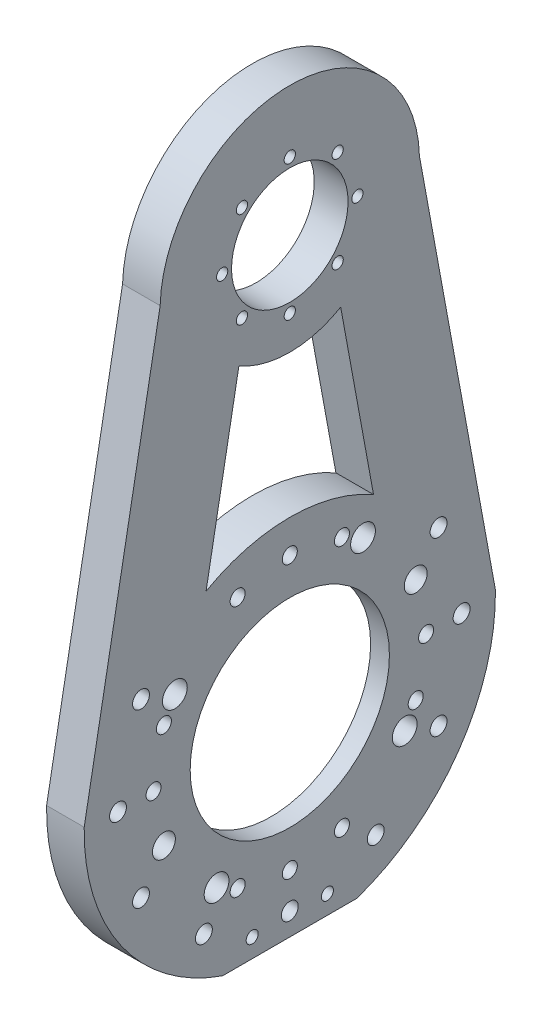
SolidWorks part; units mm, degrees
note: '?' marks a value the reader was unsure of. The reader was unsure of these and kept them because the rebuilt part matched: shared geometry of "Sketch2<5>".
ref_plane "Front Plane" through (0, 0, 0) normal (0, 0, 1) x (1, 0, 0)
ref_plane "Top Plane" through (0, 0, 0) normal (0, 1, 0) x (1, 0, 0)
ref_plane "Right Plane" through (0, 0, 0) normal (1, 0, 0) x (0, 0, -1)
sketch "Sketch2" plane through (0, 0, 0) normal (1, 0, 0) x (0, 0, -1)
  line L7 (-4.0065, 80) -> (3.9935, 80) construction
  line L8 (-44.7, 110) -> (49.7, 110) construction
  line L13 (-67.7, 0) -> (-67.7, 110)
  line L14 (67.7, 110) -> (67.7, 10)
  line L15 (67.7, -68) -> (67.7, 10)
  line L16 (-67.7, -68) -> (67.7, -68)
  line L17 (-67.7, 0) -> (-67.7, -68)
  arc A0 (-15.2865, -32.0764) -> (-12.4581, -34.9048) centre (-13.8723, -33.4906) ccw
  arc A1 (-12.4581, -34.9048) -> (-15.2865, -32.0764) centre (-13.8723, -33.4906) ccw
  arc A74 (3.7195, -20.5317) -> (1.6907, -23.1344) centre (2.7051, -21.8331) ccw
  arc A75 (1.6907, -23.1344) -> (3.7195, -20.5317) centre (2.7051, -21.8331) ccw
  arc A76 (14.2736, -16.2541) -> (12.2448, -18.8568) centre (13.2592, -17.5554) ccw
  arc A77 (12.2448, -18.8568) -> (14.2736, -16.2541) centre (13.2592, -17.5554) ccw
  arc A78 (21.275, -7.2725) -> (19.2461, -9.8752) centre (20.2605, -8.5738) ccw
  arc A79 (19.2461, -9.8752) -> (21.275, -7.2725) centre (20.2605, -8.5738) ccw
  arc A80 (22.8475, 4.0065) -> (20.8186, 1.4038) centre (21.8331, 2.7051) ccw
  arc A81 (20.8186, 1.4038) -> (22.8475, 4.0065) centre (21.8331, 2.7051) ccw
  arc A82 (18.5698, 14.5606) -> (16.541, 11.9579) centre (17.5554, 13.2592) ccw
  arc A83 (16.541, 11.9579) -> (18.5698, 14.5606) centre (17.5554, 13.2592) ccw
  arc A84 (9.5882, 21.5619) -> (7.5594, 18.9592) centre (8.5738, 20.2605) ccw
  arc A85 (7.5594, 18.9592) -> (9.5882, 21.5619) centre (8.5738, 20.2605) ccw
  arc A86 (-1.6907, 23.1344) -> (-3.7195, 20.5317) centre (-2.7051, 21.8331) ccw
  arc A87 (-3.7195, 20.5317) -> (-1.6907, 23.1344) centre (-2.7051, 21.8331) ccw
  arc A88 (-12.2448, 18.8568) -> (-14.2736, 16.2541) centre (-13.2592, 17.5554) ccw
  arc A89 (-14.2736, 16.2541) -> (-12.2448, 18.8568) centre (-13.2592, 17.5554) ccw
  arc A90 (-19.2461, 9.8752) -> (-21.275, 7.2725) centre (-20.2605, 8.5738) ccw
  arc A91 (-21.275, 7.2725) -> (-19.2461, 9.8752) centre (-20.2605, 8.5738) ccw
  arc A92 (-20.8186, -1.4038) -> (-22.8475, -4.0065) centre (-21.8331, -2.7051) ccw
  arc A93 (-22.8475, -4.0065) -> (-20.8186, -1.4038) centre (-21.8331, -2.7051) ccw
  arc A94 (-16.541, -11.9579) -> (-18.5698, -14.5606) centre (-17.5554, -13.2592) ccw
  arc A95 (-18.5698, -14.5606) -> (-16.541, -11.9579) centre (-17.5554, -13.2592) ccw
  arc A96 (-7.5594, -18.9592) -> (-9.5882, -21.5619) centre (-8.5738, -20.2605) ccw
  arc A97 (-9.5882, -21.5619) -> (-7.5594, -18.9592) centre (-8.5738, -20.2605) ccw
  arc A98 (28.2395, -17.1437) -> (32.9064, -21.8106) centre (30.5729, -19.4771) ccw
  arc A99 (32.9064, -21.8106) -> (28.2395, -17.1437) centre (30.5729, -19.4771) ccw
  arc A102 (17.1437, 32.9064) -> (21.8106, 28.2395) centre (19.4771, 30.5729) ccw
  arc A103 (21.8106, 28.2395) -> (17.1437, 32.9064) centre (19.4771, 30.5729) ccw
  arc A104 (-32.9064, 21.8106) -> (-28.2395, 17.1437) centre (-30.5729, 19.4771) ccw
  arc A105 (-28.2395, 17.1437) -> (-32.9064, 21.8106) centre (-30.5729, 19.4771) ccw
  arc A108 (-21.8106, -28.2395) -> (-17.1437, -32.9064) centre (-19.4771, -30.5729) ccw
  arc A109 (-17.1437, -32.9064) -> (-21.8106, -28.2395) centre (-19.4771, -30.5729) ccw
  arc A110 (-16.2921, -20.9002) -> (16.2921, 20.9002) centre (0, 0) ccw
  arc A111 (16.2921, 20.9002) -> (-16.2921, -20.9002) centre (0, 0) ccw
  circle A112 centre (0, 0) radius 40.5
  arc A113 (31.334, 16.029) -> (35.6473, 11.7156) centre (33.4906, 13.8723) ccw
  arc A114 (1.4142, -37.6642) -> (-1.4142, -34.8358) centre (0, -36.25) ccw
  arc A115 (-1.4142, -34.8358) -> (1.4142, -37.6642) centre (0, -36.25) ccw
  arc A116 (15.2865, -34.9048) -> (12.4581, -32.0764) centre (13.8723, -33.4906) ccw
  arc A117 (12.4581, -32.0764) -> (15.2865, -34.9048) centre (13.8723, -33.4906) ccw
  arc A118 (32.0764, -12.4581) -> (34.9048, -15.2865) centre (33.4906, -13.8723) ccw
  arc A119 (34.9048, -15.2865) -> (32.0764, -12.4581) centre (33.4906, -13.8723) ccw
  arc A120 (37.6642, -1.4142) -> (34.8358, 1.4142) centre (36.25, 0) ccw
  arc A121 (34.8358, 1.4142) -> (37.6642, -1.4142) centre (36.25, 0) ccw
  arc A122 (15.2865, 32.0764) -> (12.4581, 34.9048) centre (13.8723, 33.4906) ccw
  arc A123 (12.4581, 34.9048) -> (15.2865, 32.0764) centre (13.8723, 33.4906) ccw
  arc A124 (1.4142, 34.8358) -> (-1.4142, 37.6642) centre (0, 36.25) ccw
  arc A125 (-1.4142, 37.6642) -> (1.4142, 34.8358) centre (0, 36.25) ccw
  arc A126 (-12.4581, 32.0764) -> (-15.2865, 34.9048) centre (-13.8723, 33.4906) ccw
  arc A127 (-15.2865, 34.9048) -> (-12.4581, 32.0764) centre (-13.8723, 33.4906) ccw
  arc A128 (-34.9048, 15.2865) -> (-32.0764, 12.4581) centre (-33.4906, 13.8723) ccw
  arc A129 (-32.0764, 12.4581) -> (-34.9048, 15.2865) centre (-33.4906, 13.8723) ccw
  arc A130 (-34.8358, -1.4142) -> (-37.6642, 1.4142) centre (-36.25, 0) ccw
  arc A131 (-37.6642, 1.4142) -> (-34.8358, -1.4142) centre (-36.25, 0) ccw
  arc A134 (35.6473, 11.7156) -> (31.334, 16.029) centre (33.4906, 13.8723) ccw
  arc A135 (-31.334, -16.029) -> (-35.6473, -11.7156) centre (-33.4906, -13.8723) ccw
  arc A136 (-35.6473, -11.7156) -> (-31.334, -16.029) centre (-33.4906, -13.8723) ccw
  circle A139 centre (0, 110) radius 15.5
  arc A141 (67.7, 110) -> (-67.7, 110) centre (0, 110) ccw
  dimension "D4" = 31
  dimension "D3" = 30
extrude "Boss-Extrude1" add sketch "Sketch2" along normal blind 5
extrude "Boss-Extrude2" add sketch "Sketch2<5>" against normal blind 5
sketch "Sketch2<5>" plane through (0, 0, 0) normal (1, 0, 0) x (0, 0, -1) same geometry as "Sketch2"
sketch "Sketch7" plane through (5, 0, 0) normal (1, 0, 0) x (0, 0, -1)
  arc A0 (-32.0764, 15.2865) -> (-34.9048, 12.4581) centre (-33.4906, 13.8723) ccw
  arc A1 (-34.9048, 12.4581) -> (-32.0764, 15.2865) centre (-33.4906, 13.8723) ccw
  arc A2 (-20.5317, -3.7195) -> (-23.1344, -1.6907) centre (-21.8331, -2.7051) ccw
  arc A3 (-23.1344, -1.6907) -> (-20.5317, -3.7195) centre (-21.8331, -2.7051) ccw
  arc A4 (-16.2541, -14.2736) -> (-18.8568, -12.2448) centre (-17.5554, -13.2592) ccw
  arc A5 (-18.8568, -12.2448) -> (-16.2541, -14.2736) centre (-17.5554, -13.2592) ccw
  arc A6 (-7.2725, -21.275) -> (-9.8752, -19.2461) centre (-8.5738, -20.2605) ccw
  arc A7 (-9.8752, -19.2461) -> (-7.2725, -21.275) centre (-8.5738, -20.2605) ccw
  arc A8 (4.0065, -22.8475) -> (1.4038, -20.8186) centre (2.7051, -21.8331) ccw
  arc A9 (1.4038, -20.8186) -> (4.0065, -22.8475) centre (2.7051, -21.8331) ccw
  arc A10 (14.5606, -18.5698) -> (11.9579, -16.541) centre (13.2592, -17.5554) ccw
  arc A11 (11.9579, -16.541) -> (14.5606, -18.5698) centre (13.2592, -17.5554) ccw
  arc A12 (21.5619, -9.5882) -> (18.9592, -7.5594) centre (20.2605, -8.5738) ccw
  arc A13 (18.9592, -7.5594) -> (21.5619, -9.5882) centre (20.2605, -8.5738) ccw
  arc A14 (23.1344, 1.6907) -> (20.5317, 3.7195) centre (21.8331, 2.7051) ccw
  arc A15 (20.5317, 3.7195) -> (23.1344, 1.6907) centre (21.8331, 2.7051) ccw
  arc A16 (18.8568, 12.2448) -> (16.2541, 14.2736) centre (17.5554, 13.2592) ccw
  arc A17 (16.2541, 14.2736) -> (18.8568, 12.2448) centre (17.5554, 13.2592) ccw
  arc A18 (9.8752, 19.2461) -> (7.2725, 21.275) centre (8.5738, 20.2605) ccw
  arc A19 (7.2725, 21.275) -> (9.8752, 19.2461) centre (8.5738, 20.2605) ccw
  arc A20 (-1.4038, 20.8186) -> (-4.0065, 22.8475) centre (-2.7051, 21.8331) ccw
  arc A21 (-4.0065, 22.8475) -> (-1.4038, 20.8186) centre (-2.7051, 21.8331) ccw
  arc A22 (-11.9579, 16.541) -> (-14.5606, 18.5698) centre (-13.2592, 17.5554) ccw
  arc A23 (-14.5606, 18.5698) -> (-11.9579, 16.541) centre (-13.2592, 17.5554) ccw
  arc A24 (-18.9592, 7.5594) -> (-21.5619, 9.5882) centre (-20.2605, 8.5738) ccw
  arc A25 (-21.5619, 9.5882) -> (-18.9592, 7.5594) centre (-20.2605, 8.5738) ccw
  arc A26 (-17.1437, -28.2395) -> (-21.8106, -32.9064) centre (-19.4771, -30.5729) ccw
  arc A27 (-21.8106, -32.9064) -> (-17.1437, -28.2395) centre (-19.4771, -30.5729) ccw
  arc A28 (32.9064, -17.1437) -> (28.2395, -21.8106) centre (30.5729, -19.4771) ccw
  arc A29 (28.2395, -21.8106) -> (32.9064, -17.1437) centre (30.5729, -19.4771) ccw
  arc A30 (21.8106, 32.9064) -> (17.1437, 28.2395) centre (19.4771, 30.5729) ccw
  arc A31 (17.1437, 28.2395) -> (21.8106, 32.9064) centre (19.4771, 30.5729) ccw
  arc A32 (-28.2395, 21.8106) -> (-32.9064, 17.1437) centre (-30.5729, 19.4771) ccw
  arc A33 (-32.9064, 17.1437) -> (-28.2395, 21.8106) centre (-30.5729, 19.4771) ccw
  arc A34 (-20.9002, 16.2921) -> (20.9002, -16.2921) centre (0, 0) ccw
  arc A35 (20.9002, -16.2921) -> (-20.9002, 16.2921) centre (0, 0) ccw
  circle A36 centre (0, 0) radius 40.5
  arc A37 (16.029, -31.334) -> (11.7156, -35.6473) centre (13.8723, -33.4906) ccw
  arc A38 (-37.6642, -1.4142) -> (-34.8358, 1.4142) centre (-36.25, 0) ccw
  arc A39 (-34.8358, 1.4142) -> (-37.6642, -1.4142) centre (-36.25, 0) ccw
  arc A40 (-34.9048, -15.2865) -> (-32.0764, -12.4581) centre (-33.4906, -13.8723) ccw
  arc A41 (-32.0764, -12.4581) -> (-34.9048, -15.2865) centre (-33.4906, -13.8723) ccw
  arc A42 (-12.4581, -32.0764) -> (-15.2865, -34.9048) centre (-13.8723, -33.4906) ccw
  arc A43 (-15.2865, -34.9048) -> (-12.4581, -32.0764) centre (-13.8723, -33.4906) ccw
  arc A44 (-1.4142, -37.6642) -> (1.4142, -34.8358) centre (0, -36.25) ccw
  arc A45 (1.4142, -34.8358) -> (-1.4142, -37.6642) centre (0, -36.25) ccw
  arc A46 (32.0764, -15.2865) -> (34.9048, -12.4581) centre (33.4906, -13.8723) ccw
  arc A47 (34.9048, -12.4581) -> (32.0764, -15.2865) centre (33.4906, -13.8723) ccw
  arc A48 (34.8358, -1.4142) -> (37.6642, 1.4142) centre (36.25, 0) ccw
  arc A49 (37.6642, 1.4142) -> (34.8358, -1.4142) centre (36.25, 0) ccw
  arc A50 (32.0764, 12.4581) -> (34.9048, 15.2865) centre (33.4906, 13.8723) ccw
  arc A51 (34.9048, 15.2865) -> (32.0764, 12.4581) centre (33.4906, 13.8723) ccw
  arc A52 (15.2865, 34.9048) -> (12.4581, 32.0764) centre (13.8723, 33.4906) ccw
  arc A53 (12.4581, 32.0764) -> (15.2865, 34.9048) centre (13.8723, 33.4906) ccw
  arc A54 (-1.4142, 34.8358) -> (1.4142, 37.6642) centre (0, 36.25) ccw
  arc A55 (1.4142, 37.6642) -> (-1.4142, 34.8358) centre (0, 36.25) ccw
  arc A56 (35.1432, 35.1432) -> (-35.1432, -35.1432) centre (0, 0) ccw
  arc A57 (-35.1432, -35.1432) -> (35.1432, 35.1432) centre (0, 0) ccw
  arc A58 (11.7156, -35.6473) -> (16.029, -31.334) centre (13.8723, -33.4906) ccw
  arc A59 (-16.029, 31.334) -> (-11.7156, 35.6473) centre (-13.8723, 33.4906) ccw
  arc A60 (-11.7156, 35.6473) -> (-16.029, 31.334) centre (-13.8723, 33.4906) ccw
sketch "Sketch8" plane through (5, 0, 0) normal (1, 0, 0) x (0, 0, -1)
  line L0 (-0.0065, 60) -> (49.7, 60) construction
  line L1 (35.5, 110) -> (35.5, 60) construction
  line L2 (0, 110) -> (-0.0065, 60) construction
  line L3 (67.7, -68) -> (67.7, 110)
  line L9 (35.5, 110) -> (35.5, 60)
  line L10 (35.5, 60) -> (49.7, 60)
  line L11 (-35.5129, 60.0092) -> (-49.7129, 60.0128)
  line L12 (-35.5, 110.0092) -> (-35.5129, 60.0092)
  line L19 (67.7, -68) -> (67.7, 110)
  line L22 (-67.7, 110) -> (-67.7, -68)
  line L24 (-67.7, 110) -> (-67.7, -68)
  line L25 (-67.7, -68) -> (67.7, -68)
  line L26 (-67.7, -68) -> (67.7, -68)
  arc A1 (67.7, 110) -> (-67.7, 110) centre (0, 110) ccw
  circle A3 centre (0, 110) radius 15.5 construction
  circle A5 centre (0, 110) radius 15.5
  arc A6 (35.5, 110) -> (-35.5, 110.0092) centre (0, 110) ccw
  circle A7 centre (0, 110) radius 35.5 construction
  arc A15 (67.7, 110) -> (-67.7, 110) centre (0, 110) ccw
  dimension "D1" = 0
  dimension "D2" = 20
fillet "Fillet3" radius 1 1 edges at (-5, 0, -40.5)
sketch "Sketch9" plane through (-5, 0, 0) normal (-1, 0, 0) x (0, 0, 1)
  line L0 (0, 103.5) -> (0, 85.5) construction
  line L1 (-11.8762, 85.5) -> (11.8762, 85.5)
  line L2 (-11.8762, 85.5) -> (-11.8762, 38.1338)
  line L3 (-11.8762, 38.1338) -> (11.8762, 38.1338)
  line L4 (11.8762, 85.5) -> (11.8762, 38.1338)
  line L5 (-11.8762, 85.5) -> (11.8762, 71.7865)
  line L6 (11.8762, 71.7865) -> (-11.8762, 71.7865)
  line L7 (-11.8762, 71.7865) -> (11.8762, 58.073)
  line L8 (11.8762, 58.073) -> (-11.8762, 58.073)
  line L9 (-11.8762, 58.073) -> (11.8762, 44.3596)
  line L10 (11.8762, 44.3596) -> (-11.8762, 44.3596)
  line L11 (-11.8762, 44.3596) -> (-0.0004, 37.503)
  line L12 (-11.8762, 83.1906) -> (4.4121, 73.7865)
  line L13 (4.4121, 73.7865) -> (-11.8762, 73.7865)
  line L14 (-11.8762, 69.4771) -> (4.4121, 60.073)
  line L15 (4.4121, 60.073) -> (-11.8762, 60.073)
  line L16 (-11.8762, 55.7636) -> (4.4121, 46.3596)
  line L17 (4.4121, 46.3596) -> (-11.8762, 46.3596)
  line L18 (-11.8762, 42.0502) -> (-5.0928, 38.1338)
  line L19 (-7.8762, 85.5) -> (11.8762, 74.0959)
  line L20 (11.8762, 69.7865) -> (-4.4121, 69.7865)
  line L21 (-4.4121, 69.7865) -> (11.8762, 60.3824)
  line L22 (11.8762, 56.073) -> (-4.4121, 56.073)
  line L23 (-4.4121, 56.073) -> (11.8762, 46.669)
  line L24 (11.8762, 42.3596) -> (-4.4121, 42.3596)
  line L25 (-4.4121, 42.3596) -> (2.9072, 38.1338)
  line L26 (-0.0004, 37.503) -> (0, 38.1338) construction
  point P0 (8.8533, 58.189)
  point P37 (0, 56.8169)
sketch "Sketch12" plane through (-5, 0, 0) normal (-1, 0, 0) x (0, 0, 1)
  line L0 (0, 110) -> (-0.0015, 128) construction
  circle A2 centre (-0.0015, 128) radius 1.5
  dimension "D1" = 18
  dimension "D2" = 3
extrude "Cut-Extrude12" cut sketch "Sketch12" against normal through all
ref_axis "Axis1" through (5, 110, 0) along (-1, 0, 0)?
pattern_circular "CirPattern1" count 8 every 45 about axis through (0, 110, 0) along (1, 0, 0) of "Cut-Extrude12"
sketch "Sketch13" plane through (-5, 0, 0) normal (-1, 0, 0) x (0, 0, 1)
  circle A0 centre (0, 110) radius 21.5
  dimension "D1" = 43
extrude "Cut-Extrude13" cut sketch "Sketch13" against normal blind 1 contours A0
sketch "Sketch15" plane through (-5, 0, 0) normal (-1, 0, 0) x (0, 0, 1)
  line L0 (-34.4859, 110.9876) -> (-54.6916, 0.9561)
  line L2 (-24.5, 110) -> (-44.7, 0)
  line L3 (24.5, 110) -> (44.7, 0)
  line L4 (34.4859, 110.9876) -> (54.6916, 0.9561)
  line L5 (67.7, -68) -> (67.7, 110) construction
  line L6 (67.7, -68) -> (-67.7, -68) construction
  line L7 (-67.7, 110) -> (-67.7, -68) construction
  line L8 (67.7, -68) -> (67.7, 110)
  line L9 (67.7, -68) -> (-67.7, -68)
  line L10 (-67.7, 110) -> (-67.7, -68)
  arc A4 (-44.7, 0) -> (44.7, 0) centre (0, 0) ccw
  arc A5 (24.5, 110) -> (-24.5, 110) centre (0, 110) ccw
  arc A6 (34.4859, 110.9876) -> (-34.4859, 110.9876) centre (0, 110) ccw
  arc A7 (-54.6916, 0.9561) -> (54.6916, 0.9561) centre (0, 0) ccw
  arc A8 (67.7, 110) -> (-67.7, 110) centre (0, 110) ccw construction
  arc A9 (67.7, 110) -> (-67.7, 110) centre (0, 110) ccw
  line M54 (-67.7, 110) -> (-67.7, -68)
  line M55 (-67.7, -68) -> (67.7, -68)
  line M56 (67.7, -68) -> (67.7, 110)
  arc M57 (67.7, 110) -> (-67.7, 110) centre (0, 110) ccw
  dimension "D1" = 10
extrude "Cut-Extrude16" cut sketch "Sketch15" against normal blind 10 contours A7 L0 A6 L4 M57 M54 M55 M56
sketch "Sketch16" plane through (-5, 0, 0) normal (-1, 0, 0) x (0, 0, 1)
  line L0 (-51.5212, -51.7) -> (53.7322, -51.7)
  line L1 (0, -54.7) -> (0, -51.7) construction
  line L2 (-51.5212, -51.7) -> (-51.5212, -61.7658)
  line L3 (-51.5212, -61.7658) -> (53.7322, -61.7658)
  line L4 (53.7322, -61.7658) -> (53.7322, -51.7)
  arc A0 (-54.6916, 0.9561) -> (54.6916, 0.9561) centre (0, 0) ccw construction
  dimension "D1" = 3
extrude "Cut-Extrude17" cut sketch "Sketch16" against normal blind 10
sketch "Sketch18" plane through (-5, 0, 0) normal (-1, 0, 0) x (0, 0, 1)
  line L2 (-24.5, 110) -> (-44.7, 0)
  line L9 (44.7, 0) -> (24.5, 110)
  line L10 (-24.5, 110) -> (-44.7, 0)
  line L11 (44.7, 0) -> (24.5, 110)
  line L12 (-34.4859, 110.9876) -> (-54.6916, 0.9561)
  line L13 (54.6916, 0.9561) -> (34.4859, 110.9876)
  line L14 (-34.4859, 110.9876) -> (-54.6916, 0.9561)
  line L15 (54.6916, 0.9561) -> (34.4859, 110.9876)
  arc A4 (-44.7, 0) -> (44.7, 0) centre (0, 0) ccw
  arc A5 (24.5, 110) -> (-24.5, 110) centre (0, 110) ccw
  arc A6 (-44.7, 0) -> (44.7, 0) centre (0, 0) ccw
  arc A7 (24.5, 110) -> (-24.5, 110) centre (0, 110) ccw
  arc A8 (-54.6916, 0.9561) -> (54.6916, 0.9561) centre (0, 0) ccw
  arc A9 (34.4859, 110.9876) -> (-34.4859, 110.9876) centre (0, 110) ccw
  arc A10 (-54.6916, 0.9561) -> (54.6916, 0.9561) centre (0, 0) ccw
  arc A11 (34.4859, 110.9876) -> (-34.4859, 110.9876) centre (0, 110) ccw
  dimension "D2" = 0
  dimension "D3" = 0
sketch "Sketch19" plane through (5, 0, 0) normal (1, 0, 0) x (0, 0, -1)
  line L0 (22.2683, 39.104) -> (13.539, 86.6398)
  line L1 (-13.539, 86.6398) -> (-22.2683, 39.104)
  line L2 (44.7, 0) -> (24.5, 110)
  line L3 (-24.5, 110) -> (-44.7, 0)
  line L4 (44.7, 0) -> (24.5, 110)
  line L5 (-24.5, 110) -> (-44.7, 0)
  line L6 (-34.4859, 110.9876) -> (-54.6916, 0.9561)
  line L7 (54.6916, 0.9561) -> (34.4859, 110.9876)
  line L8 (-34.4859, 110.9876) -> (-54.6916, 0.9561)
  line L9 (54.6916, 0.9561) -> (34.4859, 110.9876)
  line L10 (-9.4419, 108.9507) -> (-29.9467, -2.7092) construction
  line L11 (29.9467, -2.7092) -> (9.4419, 108.9507) construction
  arc A0 (-13.539, 86.6398) -> (13.539, 86.6398) centre (0, 110) ccw
  arc A1 (22.2683, 39.104) -> (-22.2683, 39.104) centre (0, 0) ccw
  arc A2 (-44.7, 0) -> (44.7, 0) centre (0, 0) ccw
  arc A3 (24.5, 110) -> (-24.5, 110) centre (0, 110) ccw
  arc A4 (-44.7, 0) -> (44.7, 0) centre (0, 0) ccw
  arc A5 (24.5, 110) -> (-24.5, 110) centre (0, 110) ccw
  arc A6 (-54.6916, 0.9561) -> (54.6916, 0.9561) centre (0, 0) ccw
  arc A7 (34.4859, 110.9876) -> (-34.4859, 110.9876) centre (0, 110) ccw
  arc A8 (-54.6916, 0.9561) -> (54.6916, 0.9561) centre (0, 0) ccw
  arc A9 (34.4859, 110.9876) -> (-34.4859, 110.9876) centre (0, 110) ccw
  arc A10 (9.4419, 108.9507) -> (-9.4419, 108.9507) centre (0, 110) ccw construction
  dimension "D4" = 54
  dimension "D5" = 90
  dimension "D1" = 0
  dimension "D2" = 0
  dimension "D3" = 15
extrude "Cut-Extrude20" cut sketch "Sketch19" against normal through all contours A1 L0 A0 L1
sketch "Sketch20" plane through (5, 0, 0) normal (1, 0, 0) x (0, 0, -1)
  line L2 (-34.4859, 110.9876) -> (-54.6916, 0.9561)
  line L3 (-17.8662, -51.7) -> (17.8662, -51.7)
  line L4 (54.6916, 0.9561) -> (34.4859, 110.9876)
  line L5 (-34.4859, 110.9876) -> (-54.6916, 0.9561)
  line L6 (-17.8662, -51.7) -> (17.8662, -51.7)
  line L7 (54.6916, 0.9561) -> (34.4859, 110.9876)
  line L8 (-34.4859, 110.9876) -> (-54.6916, 0.9561)
  line L9 (54.6916, 0.9561) -> (34.4859, 110.9876)
  line L10 (-34.4859, 110.9876) -> (-54.6916, 0.9561)
  line L11 (54.6916, 0.9561) -> (34.4859, 110.9876)
  line L12 (44.7, 0) -> (24.5, 110)
  line L13 (-24.5, 110) -> (-44.7, 0)
  line L14 (44.7, 0) -> (24.5, 110)
  line L15 (-24.5, 110) -> (-44.7, 0)
  arc A2 (-54.6916, 0.9561) -> (54.6916, 0.9561) centre (0, 0) ccw
  arc A3 (17.8662, -51.7) -> (54.6916, 0.9561) centre (0, 0) ccw
  arc A4 (34.4859, 110.9876) -> (-34.4859, 110.9876) centre (0, 110) ccw
  arc A5 (-54.6916, 0.9561) -> (-17.8662, -51.7) centre (0, 0) ccw
  arc A6 (17.8662, -51.7) -> (54.6916, 0.9561) centre (0, 0) ccw
  arc A7 (34.4859, 110.9876) -> (-34.4859, 110.9876) centre (0, 110) ccw
  arc A8 (-54.6916, 0.9561) -> (-17.8662, -51.7) centre (0, 0) ccw
  arc A9 (34.4859, 110.9876) -> (-34.4859, 110.9876) centre (0, 110) ccw
  arc A10 (-54.6916, 0.9561) -> (54.6916, 0.9561) centre (0, 0) ccw
  arc A11 (34.4859, 110.9876) -> (-34.4859, 110.9876) centre (0, 110) ccw
  arc A12 (24.5, 110) -> (-24.5, 110) centre (0, 110) ccw
  arc A13 (-44.7, 0) -> (44.7, 0) centre (0, 0) ccw
  arc A14 (24.5, 110) -> (-24.5, 110) centre (0, 110) ccw
  arc A15 (-44.7, 0) -> (44.7, 0) centre (0, 0) ccw
  dimension "D1" = 0
  dimension "D2" = 0
  dimension "D3" = 0
sketch "Sketch29" plane through (5, 0, 0) normal (1, 0, 0) x (0, 0, -1)
  line L0 (0, -51.7) -> (0, -46.7) construction
  line L1 (-17.8662, -51.7) -> (17.8662, -51.7) construction
  line L2 (0, -46.7) -> (10, -46.7) construction
  line L3 (0, -46.7) -> (-10, -46.7) construction
  circle A0 centre (-10, -46.7) radius 1.6
  circle A1 centre (10, -46.7) radius 1.6
  dimension "D3" = 3.2
  dimension "D1" = 5
  dimension "D2" = 10
extrude "Cut-Extrude21" cut sketch "Sketch29" against normal blind 10
sketch "Sketch31" plane through (5, 0, 0) normal (1, 0, 0) x (0, 0, -1)
  line L0 (0, 0) -> (0, -45.7) construction
  circle A0 centre (0, -45.7) radius 2.25
  dimension "D2" = 4.5
  dimension "D1" = 45.7
extrude "Cut-Extrude22" cut sketch "Sketch31" against normal blind 10
ref_axis "Axis2" through (5, 0, 0) along (-1, 0, 0)?
pattern_circular "CirPattern2" count 5 every 30 about axis through (0, 0, 0) along (1, 0, 0) of "Cut-Extrude22"
